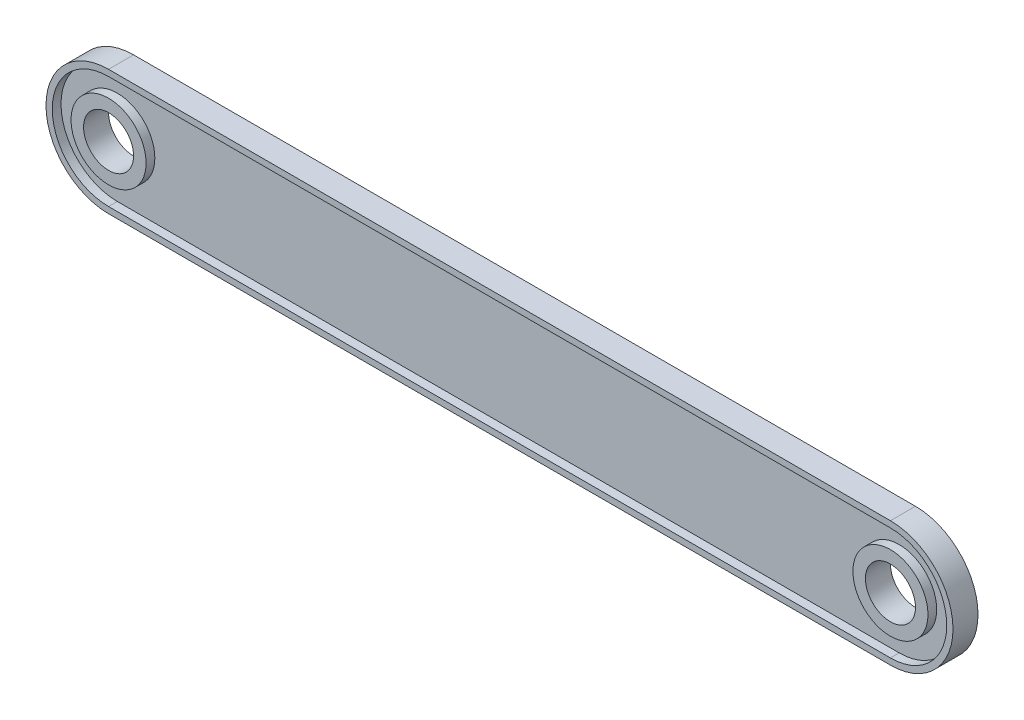
SolidWorks part; units mm, degrees
ref_plane "Front Plane" through (0, 0, 0) normal (0, 0, 1) x (1, 0, 0)
ref_plane "Top Plane" through (0, 0, 0) normal (0, 1, 0) x (1, 0, 0)
ref_plane "Right Plane" through (0, 0, 0) normal (1, 0, 0) x (0, 0, -1)
sketch "Sketch1" plane through (0, 0, 0) normal (0, 0, 1) x (1, 0, 0)
  line L0 (0, 0) -> (-625, 0) construction
  line L1 (0, 50) -> (-625, 50)
  line L2 (0, -50) -> (-625, -50)
  arc A0 (0, 50) -> (0, -50) centre (0, 0) cw
  arc A1 (-625, 50) -> (-625, -50) centre (-625, 0) ccw
  circle A3 centre (0, 0) radius 20
  circle A4 centre (-625, 0) radius 20
  dimension "D4" = 40
  dimension "D3" = 625
  dimension "D1" = 50
  dimension "D2" = 50
extrude "Extrude1" add sketch "Sketch1" along normal mid plane 20
ref_axis "Axis1" through (-625, 0, 0) along (1, 0, 0)
sketch "Sketch2" plane through (0, 0, 10) normal (0, 0, 1) x (1, 0, 0)
  line L4 (0, 45) -> (-625, 45)
  line L5 (-625, -45) -> (0, -45)
  line L6 (0, 45) -> (-625, 45)
  line L7 (-625, -45) -> (0, -45)
  arc A4 (0, -45) -> (0, 45) centre (0, 0) ccw
  arc A5 (-625, 45) -> (-625, -45) centre (-625, 0) ccw
  arc A6 (0, -45) -> (0, 45) centre (0, 0) ccw
  arc A7 (-625, 45) -> (-625, -45) centre (-625, 0) ccw
  circle A11 centre (0, 0) radius 30
  circle A12 centre (0, 0) radius 30
  circle A14 centre (-625, 0) radius 30
  circle A15 centre (-625, 0) radius 30
  dimension "D1" = 5
  dimension "D2" = 10
  dimension "D3" = 10
extrude "Cut-Extrude1" cut sketch "Sketch2" against normal offset from surface (7 mm away) 3 up to plane "Front Plane"
mirror "Mirror1" about plane through (0, 0, 0) normal (0, 0, 1) of "Cut-Extrude1"
